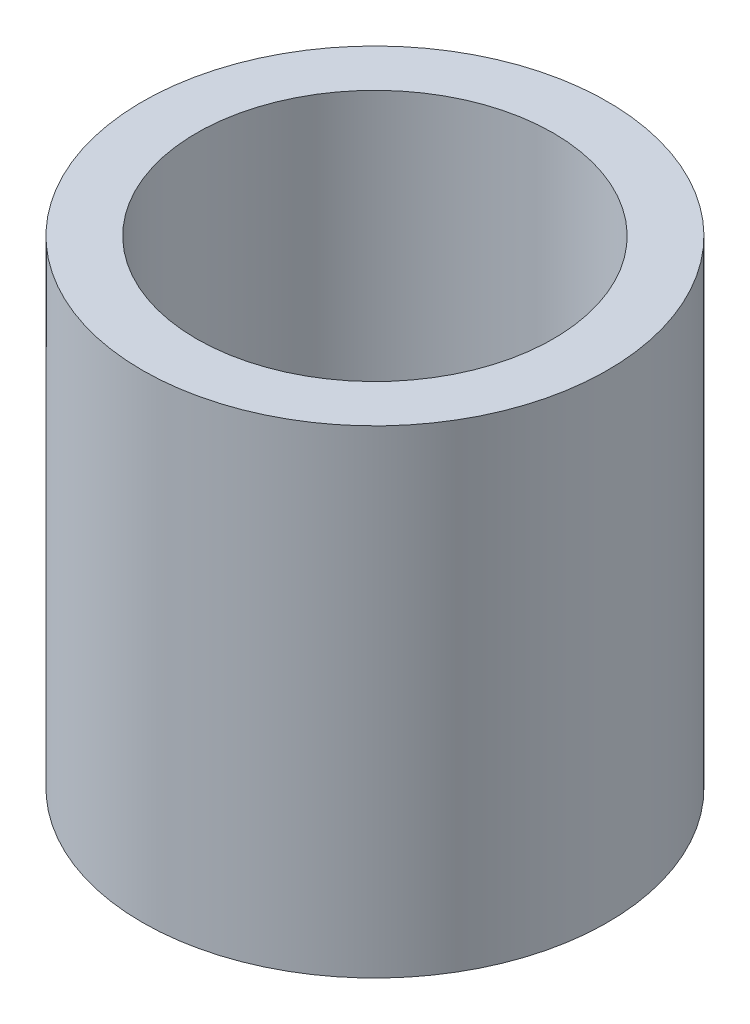
SolidWorks part; units mm, degrees
material "PTFE (general)"
ref_plane "Front Plane" through (0, 0, 0) normal (0, 0, 1) x (1, 0, 0)
ref_plane "Top Plane" through (0, 0, 0) normal (0, 1, 0) x (1, 0, 0)
ref_plane "Right Plane" through (0, 0, 0) normal (1, 0, 0) x (0, 0, -1)
sketch "Sketch1" plane through (0, 0, 0) normal (0, 1, 0) x (1, 0, 0)
  circle A0 centre (0, 0) radius 6.9
  circle A1 centre (0, 0) radius 9
  dimension "D1" = 18
  dimension "D2" = 13.8
extrude "Boss-Extrude1" add sketch "Sketch1" along normal blind 18.5
